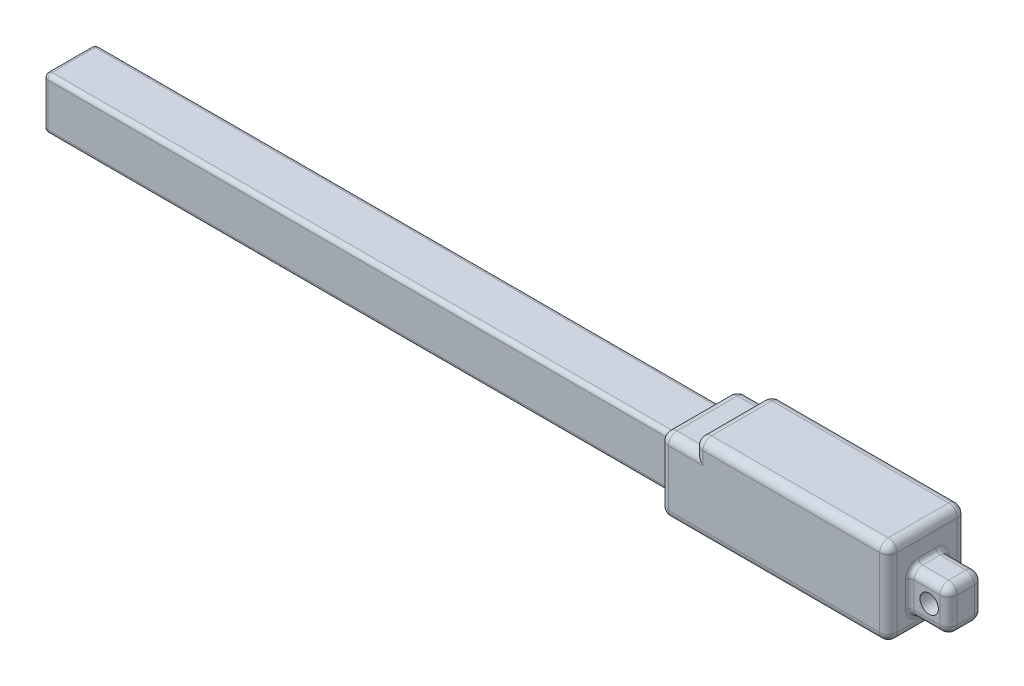
SolidWorks part; units mm, degrees
ref_plane "Front Plane" through (0, 0, 0) normal (0, 0, 1) x (1, 0, 0)
ref_plane "Top Plane" through (0, 0, 0) normal (0, 1, 0) x (1, 0, 0)
ref_plane "Right Plane" through (0, 0, 0) normal (1, 0, 0) x (0, 0, -1)
sketch "Sketch1" plane through (0, 0, 0) normal (0, 0, 1) x (1, 0, 0)
  line L1 (0, 8.5) -> (53, 8.5)
  line L2 (0, 8.5) -> (0, -8.5)
  line L3 (0, -8.5) -> (53, -8.5)
  line L4 (53, 8.5) -> (53, -8.5)
  dimension "D1" = 53
  dimension "D2" = 8.5
  dimension "D3" = 8.5
extrude "Boss-Extrude1" add sketch "Sketch1" along normal blind 9 and the other way blind 9
sketch "Sketch2" plane through (0, 8.5, 0) normal (0, 1, 0) x (1, 0, 0)
  line L0 (53, 9) -> (0, 9) construction
  line L1 (53, -9) -> (0, -9) construction
  line L2 (53, 9) -> (53, -9) construction
  line L3 (53, 9) -> (8, 9)
  line L4 (53, -9) -> (8, -9)
  line L5 (53, 9) -> (53, -9)
  line L6 (8, 9) -> (8, -9)
  dimension "D1" = 45
extrude "Boss-Extrude2" add sketch "Sketch2" along normal blind 3
sketch "Sketch3" plane through (53, 0, 0) normal (1, 0, 0) x (0, 0, -1)
  line L0 (9, -8.5) -> (-9, -8.5) construction
  line L1 (-4, -5) -> (4, -5)
  line L2 (-4, -5) -> (-4, 5)
  line L3 (-4, 5) -> (4, 5)
  line L4 (4, -5) -> (4, 5)
  point P4 (0, -8.5)
  dimension "D1" = 4
  dimension "D2" = 8
  dimension "D3" = 10
  dimension "D4" = 3.5
extrude "Boss-Extrude3" add sketch "Sketch3" along normal blind 9
sketch "Sketch4" plane through (0, 0, 0) normal (-1, 0, 0) x (0, 0, 1)
  line L0 (-6, -6) -> (6, -6)
  line L1 (-6, -6) -> (-6, 6)
  line L2 (6, -6) -> (6, 6)
  line L3 (-6, 6) -> (6, 6)
  line L4 (-6, -6) -> (6, 6) construction
  line L5 (6, -6) -> (-6, 6) construction
  dimension "D1" = 12
extrude "Boss-Extrude4" add sketch "Sketch4" along normal blind 146
sketch "Sketch6" plane through (0, 0, 4) normal (0, 0, 1) x (1, 0, 0)
  line L0 (62, 5) -> (62, -5) construction
  line L1 (62, 5) -> (53, 5) construction
  circle A0 centre (57.5, 0) radius 2.125
  dimension "D1" = 4.5
  dimension "D2" = 5
extrude "Cut-Extrude1" cut sketch "Sketch6" against normal up to next
fillet "Fillet2" radius 2 25 edges at (53, 1.5, 9) (0, 0, 9) (30.5, 11.5, 9) (8, 11.5, 0) (30.5, 11.5, -9) (53, 11.5, 0) (26.5, -8.5, -9) (0, -8.5, 0) (26.5, -8.5, 9) (53, -8.5, 0) (57.5, -5, -4) (62, 0, -4) (62, -5, 0) (57.5, -5, 4) (62, 0, 4) (0, 8.5, 0) (0, 0, -9) (57.5, 5, 4) (62, 5, 0) (57.5, 5, -4) (53, 1.5, -9)
fillet "Fillet3" radius 1 8 edges at (53, -4.4142, 3.4142) (53, 0, 4) (53, 4.4142, 3.4142) (53, 5, 0) (53, 4.4142, -3.4142) (53, 0, -4) (53, -4.4142, -3.4142) (53, -5, 0)
sketch "Sketch7" plane through (-146, 0, 0) normal (-1, 0, 0) x (0, 0, 1)
  circle A0 centre (0, 0) radius 4.5
  dimension "D1" = 9
extrude "Cut-Extrude2" cut sketch "Sketch7" against normal blind 140
fillet "Fillet4" radius 1 8 edges at (-146, 0, -6) (-146, -6, 0) (-73, -6, 6) (-73, -6, -6) (-146, 6, 0) (-73, 6, -6) (-146, 0, 6) (-73, 6, 6)
